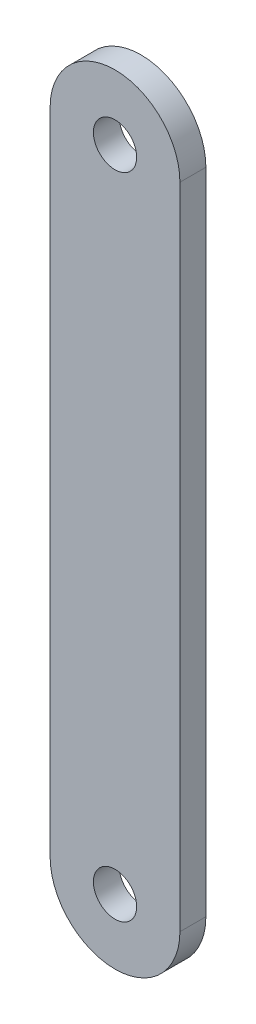
SolidWorks part; units mm, degrees
ref_plane "Front Plane" through (0, 0, 0) normal (0, 0, 1) x (1, 0, 0)
ref_plane "Top Plane" through (0, 0, 0) normal (0, 1, 0) x (1, 0, 0)
ref_plane "Right Plane" through (0, 0, 0) normal (1, 0, 0) x (0, 0, -1)
sketch "Sketch1" plane through (0, 0, 0) normal (0, 0, 1) x (1, 0, 0)
  line L2 (185.8254, 60.5329) -> (185.8254, 135.5329)
  line L4 (200.8254, 60.5329) -> (200.8254, 135.5329)
  arc A0 (185.8254, 60.5329) -> (200.8254, 60.5329) centre (193.3254, 60.5329) ccw
  arc A1 (200.8254, 135.5329) -> (185.8254, 135.5329) centre (193.3254, 135.5329) ccw
  circle A2 centre (193.3254, 60.5329) radius 2.5
  circle A3 centre (193.3254, 135.5329) radius 2.5
  dimension "D3" = 5
  dimension "D4" = 5
  dimension "D1" = 15
  dimension "D2" = 75
extrude "Boss-Extrude1" add sketch "Sketch1" along normal blind 3
